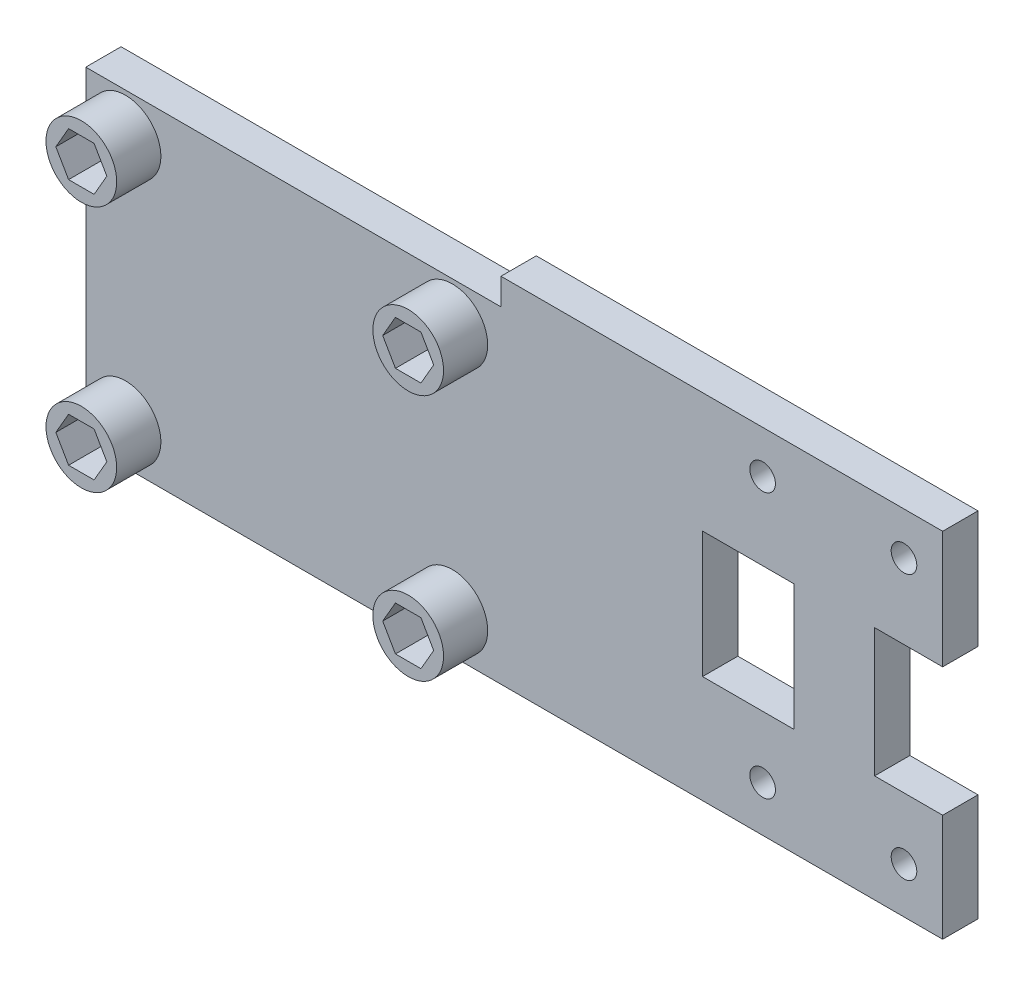
SolidWorks part; units mm, degrees
ref_plane "Front Plane" through (0, 0, 0) normal (0, 0, 1) x (1, 0, 0)
ref_plane "Top Plane" through (0, 0, 0) normal (0, 1, 0) x (1, 0, 0)
ref_plane "Right Plane" through (0, 0, 0) normal (1, 0, 0) x (0, 0, -1)
ref_plane "Plane1" through (0, 0, 34.8116) normal (0, 0, -1) x (-1, 0, 0)
sketch "Sketch1" plane through (0, 0, 34.8116) normal (0, 0, -1) x (-1, 0, 0)
  line L0 (-23.5355, 118.8347) -> (-23.5355, 78.8347)
  line L1 (-23.5355, 78.8347) -> (26.4645, 78.8347)
  line L2 (26.4645, 78.8347) -> (26.4645, 118.8347)
  line L3 (26.4645, 118.8347) -> (-23.5355, 118.8347)
extrude "Boss-Extrude1" add sketch "Sketch1" against normal blind 4
sketch "Sketch2" plane through (0, 0, 38.8116) normal (0, 0, 1) x (1, 0, 0)
  line L0 (23.5355, 90.9981) -> (23.5355, 105.5372)
  line L1 (23.5355, 105.5372) -> (15.8296, 105.5372)
  line L2 (15.8296, 105.5372) -> (15.8296, 90.9981)
  line L3 (15.8296, 90.9981) -> (23.5355, 90.9981)
extrude "Cut-Extrude1" cut sketch "Sketch2" against normal through all
sketch "Sketch3" plane through (0, 0, 38.8116) normal (0, 0, 1) x (1, 0, 0)
  line L0 (6.7257, 105.2654) -> (-3.6465, 105.2654)
  line L1 (-3.6465, 105.2654) -> (-3.6465, 90.9981)
  line L2 (-3.6465, 90.9981) -> (6.7257, 90.9981)
  line L3 (6.7257, 90.9981) -> (6.7257, 105.2654)
extrude "Cut-Extrude2" cut sketch "Sketch3" against normal through all
hole_wizard "CSK for M2.5 Flat Head Machine Screw1" positions "Sketch5" profile "Sketch4" countersink size "M2.5" standard "ANSI Metric" end condition through all
sketch "Sketch5" plane through (0, 0, 34.8116) normal (0, 0, -1) x (-1, 0, 0)
  point P0 (-3.1566, 84.0163)
  point P1 (-19.1566, 84.0163)
  point P2 (-19.1566, 114.0163)
  point P3 (-3.1566, 114.0163)
sketch "Sketch4" plane through (3.1566, 84.0163, 34.8116) normal (1, 0, 0) x (0, 1, 0)
  line L0 (0, 0) -> (0, 4)
  line L1 (0, 4) -> (1.45, 4)
  line L2 (1.45, 4) -> (1.45, 1.3)
  line L3 (1.45, 1.3) -> (2.75, 0)
  line L5 (2.75, 0) -> (0, 0)
  line L6 (-1.45, 1.3) -> (-2.75, 0) construction
  line L11 (0, -6.35) -> (0, 107.95) construction
  dimension "Thru Hole Dia." = 2.9
  dimension "Thru Hole Depth" = 4
  dimension "Near C'Sink Dia." = 5.5
  dimension "Near C'Sink Angle" = 90
sketch "Sketch6" plane through (0, 0, 38.8116) normal (0, 0, 1) x (1, 0, 0)
  line L1 (-26.4645, 78.8347) -> (-73.4645, 78.8347)
  line L2 (-26.4645, 78.8347) -> (-26.4645, 115.8347)
  line L3 (-26.4645, 115.8347) -> (-73.4645, 115.8347)
  line L4 (-73.4645, 78.8347) -> (-73.4645, 115.8347)
  dimension "D1" = 47
  dimension "D2" = 37
extrude "Boss-Extrude2" add sketch "Sketch6" against normal up to surface (4 mm away) up to face at (0.4066, 84.0163, 34.8116)
sketch "Sketch7" plane through (0, 0, 38.8116) normal (0, 0, 1) x (1, 0, 0)
  line L0 (-68.9645, 111.3347) -> (-68.9645, 83.3347) construction
  line L1 (-73.4645, 97.3347) -> (-68.9645, 97.3347) construction
  line L2 (-73.4645, 115.8347) -> (-73.4645, 78.8347) construction
  line L3 (-26.4645, 115.8347) -> (-26.4645, 118.8347) construction
  circle A0 centre (-68.9645, 111.3347) radius 4
  circle A1 centre (-31.9645, 111.3347) radius 4
  circle A2 centre (-68.9645, 83.3347) radius 4
  circle A3 centre (-31.9645, 83.3347) radius 4
  dimension "D3" = 8
  dimension "D1" = 37
  dimension "D2" = 28
  dimension "D4" = 5.5
extrude "Boss-Extrude3" add sketch "Sketch7" along normal blind 5
hole_wizard "Ø2.7 (2.7) Diameter Hole1" positions "Sketch8" profile "Sketch9" hole size "Ø2.7" standard "ANSI Metric"
sketch "Sketch8" plane through (0, 0, 43.8116) normal (0, 0, 1) x (1, 0, 0)
  point P0 (-68.9645, 111.3347)
  point P3 (-31.9645, 111.3347)
  point P6 (-31.9645, 83.3347)
  point P9 (-68.9645, 83.3347)
sketch "Sketch9" plane through (-68.9645, 111.3347, 43.8116) normal (1, 0, 0) x (0, -1, 0)
  line L0 (0, 0) -> (0, 4.8112)
  line L1 (0, 4.8112) -> (1.35, 4)
  line L2 (1.35, 4) -> (1.35, 0)
  line L5 (1.35, 0) -> (0, 0)
  line L10 (0, 4.8112) -> (-1.35, 4) construction
  line L11 (0, -6.35) -> (0, 107.95) construction
  dimension "Hole Dia." = 2.7
  dimension "Hole Depth" = 4
  dimension "Drill Angle" = 118
sketch "Sketch10" plane through (0, 0, 43.8116) normal (0, 0, 1) x (1, 0, 0)
  line L0 (-26.4645, 115.8347) -> (-73.4645, 115.8347) construction
  line L1 (-67.5211, 113.8347) -> (-70.4078, 113.8347)
  line L2 (-70.4078, 113.8347) -> (-71.8512, 111.3347)
  line L3 (-71.8512, 111.3347) -> (-70.4078, 108.8347)
  line L4 (-70.4078, 108.8347) -> (-67.5211, 108.8347)
  line L5 (-67.5211, 108.8347) -> (-66.0777, 111.3347)
  line L6 (-66.0777, 111.3347) -> (-67.5211, 113.8347)
  line L8 (-67.5211, 85.8347) -> (-70.4078, 85.8347)
  line L9 (-70.4078, 85.8347) -> (-71.8512, 83.3347)
  line L10 (-71.8512, 83.3347) -> (-70.4078, 80.8347)
  line L11 (-70.4078, 80.8347) -> (-67.5211, 80.8347)
  line L12 (-67.5211, 80.8347) -> (-66.0777, 83.3347)
  line L13 (-66.0777, 83.3347) -> (-67.5211, 85.8347)
  line L14 (-30.5211, 113.8347) -> (-33.4078, 113.8347)
  line L15 (-33.4078, 113.8347) -> (-34.8512, 111.3347)
  line L16 (-34.8512, 111.3347) -> (-33.4078, 108.8347)
  line L17 (-33.4078, 108.8347) -> (-30.5211, 108.8347)
  line L18 (-30.5211, 108.8347) -> (-29.0777, 111.3347)
  line L19 (-29.0777, 111.3347) -> (-30.5211, 113.8347)
  line L20 (-30.5211, 85.8347) -> (-33.4078, 85.8347)
  line L21 (-33.4078, 85.8347) -> (-34.8512, 83.3347)
  line L22 (-34.8512, 83.3347) -> (-33.4078, 80.8347)
  line L23 (-33.4078, 80.8347) -> (-30.5211, 80.8347)
  line L24 (-30.5211, 80.8347) -> (-29.0777, 83.3347)
  line L25 (-29.0777, 83.3347) -> (-30.5211, 85.8347)
  circle A0 centre (-68.9645, 111.3347) radius 2.5 construction
  circle A1 centre (-68.9645, 83.3347) radius 2.5 construction
  circle A2 centre (-31.9645, 111.3347) radius 2.5 construction
  circle A3 centre (-31.9645, 83.3347) radius 2.5 construction
  dimension "D1" = 5
extrude "Cut-Extrude3" cut sketch "Sketch10" against normal blind 6.5
